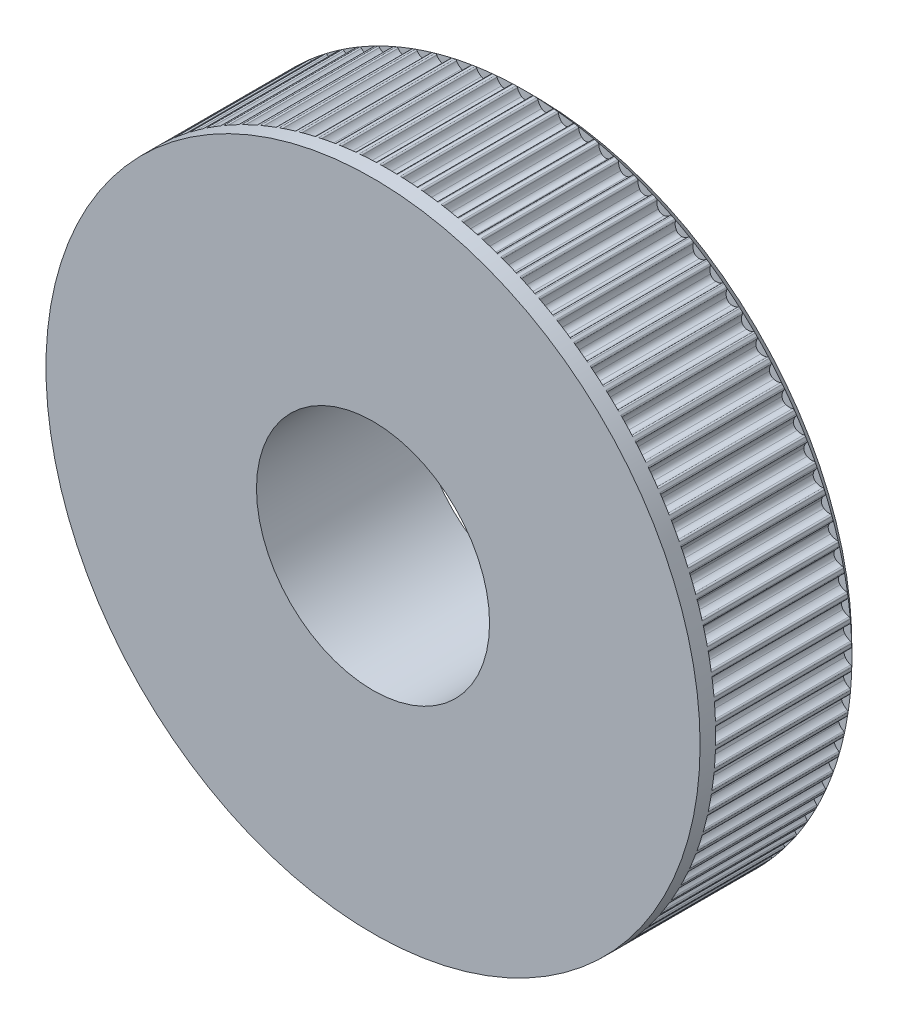
SolidWorks part; units mm, degrees
ref_plane "Front Plane" through (0, 0, 0) normal (0, 0, 1) x (1, 0, 0)
ref_plane "Top Plane" through (0, 0, 0) normal (0, 1, 0) x (1, 0, 0)
ref_plane "Right Plane" through (0, 0, 0) normal (1, 0, 0) x (0, 0, -1)
sketch "Sketch1" plane through (0, 0, 0) normal (0, 0, 1) x (1, 0, 0)
  line L3 (0, 31.5722) -> (1.999, 31.5089) construction
  line L4 (0, 0) -> (0, 30.8222) construction
  line L5 (0, 30.8222) -> (0, 32.1035) construction
  line L15 (1.999, 31.5089) -> (2.0367, 32.1035)
  line L16 (2.0367, 32.1035) -> (-2.0367, 32.1035)
  line L17 (0, 30.8222) -> (0.1538, 30.8222) construction
  line L18 (-1.999, 31.5089) -> (-2.0367, 32.1035)
  circle A0 centre (0, 0) radius 31.826 construction
  circle A1 centre (0, 0) radius 31.5722 construction
  circle A2 centre (0, 0) radius 31.3182 construction
  arc A10 (0.8511, 31.5607) -> (1.999, 31.5089) centre (0, 0) cw
  arc A11 (-0.3168, 30.9215) -> (0.3168, 30.9215) centre (0, 31.3772) ccw
  arc A12 (0.3168, 30.9215) -> (0.7035, 31.4541) centre (-0.254, 31.7426) ccw
  arc A13 (0.7035, 31.4541) -> (0.8511, 31.5607) centre (0.8471, 31.4108) cw
  arc A14 (-0.8511, 31.5607) -> (-1.999, 31.5089) centre (0, 0) ccw
  arc A15 (-0.7035, 31.4541) -> (-0.8511, 31.5607) centre (-0.8471, 31.4108) ccw
  arc A16 (-0.3168, 30.9215) -> (-0.7035, 31.4541) centre (0.254, 31.7426) cw
  point P11 (0, 31.826)
  point P13 (0, 31.5722)
  point P14 (0, 31.3182)
  dimension "D2" = 0.2775
sketch "Sketch2" plane through (0, 0, 0) normal (1, 0, 0) x (0, 0, -1)
  line L0 (-3.625, 11.25) -> (9.525, 11.25)
  line L3 (-3.625, 11.25) -> (-3.625, 31.5722)
  line L9 (9.525, 31.5722) -> (9.525, 11.25)
  line L10 (-9.525, 0) -> (9.525, 0) construction
  line L16 (-3.625, 31.5722) -> (9.525, 31.5722)
  point P25 (9.525, 0)
  point P26 (-3.625, 0)
  dimension "OA" = 19.05
  dimension "Bore" = 22.5
  dimension "Outside Width" = 13.15
revolve "Revolve1" add sketch "Sketch2" angle 360 mid plane about L10
sketch "Sketch3" plane through (0, 0, 0) normal (0, 0, 1) x (1, 0, 0)
  line L3 (1.999, 31.5089) -> (2.0367, 32.1035) construction
  line L4 (-1.999, 31.5089) -> (-2.0367, 32.1035) construction
  line L5 (2.0367, 32.1035) -> (-2.0367, 32.1035) construction
  line L6 (1.999, 31.5089) -> (2.0367, 32.1035)
  line L7 (-1.999, 31.5089) -> (-2.0367, 32.1035)
  line L8 (2.0367, 32.1035) -> (-2.0367, 32.1035)
  arc A0 (1.999, 31.5089) -> (0.8511, 31.5607) centre (0, 0) ccw construction
  arc A1 (0.8511, 31.5607) -> (0.7035, 31.4541) centre (0.8471, 31.4108) ccw construction
  arc A3 (0.3168, 30.9215) -> (0.7035, 31.4541) centre (-0.254, 31.7426) ccw construction
  arc A4 (-0.3168, 30.9215) -> (0.3168, 30.9215) centre (0, 31.3772) ccw construction
  arc A5 (-0.7035, 31.4541) -> (-0.3168, 30.9215) centre (0.254, 31.7426) ccw construction
  arc A6 (-0.7035, 31.4541) -> (-0.8511, 31.5607) centre (-0.8471, 31.4108) ccw construction
  arc A7 (-0.8511, 31.5607) -> (-1.999, 31.5089) centre (0, 0) ccw construction
  arc A8 (1.999, 31.5089) -> (0.8511, 31.5607) centre (0, 0) ccw
  arc A9 (0.8511, 31.5607) -> (0.7035, 31.4541) centre (0.8471, 31.4108) ccw
  arc A10 (0.3168, 30.9215) -> (0.7035, 31.4541) centre (-0.254, 31.7426) ccw
  arc A11 (-0.3168, 30.9215) -> (0.3168, 30.9215) centre (0, 31.3772) ccw
  arc A12 (-0.7035, 31.4541) -> (-0.3168, 30.9215) centre (0.254, 31.7426) ccw
  arc A13 (-0.7035, 31.4541) -> (-0.8511, 31.5607) centre (-0.8471, 31.4108) ccw
  arc A14 (-0.8511, 31.5607) -> (-1.999, 31.5089) centre (0, 0) ccw
extrude "Cut-Extrude1" cut sketch "Sketch3" against normal through all from surface starting at face at (11.25, 0, 3.625)
pattern_circular "CirPattern1" count 100 over 360 about axis through (0, 0, 9.525) along (0, 0, 1) of "Cut-Extrude1"
ref_axis "Center Axis 1" through (0, 0, -9.525) along (0, 0, 1)
ref_plane "Contact Plane 2" through (0, 0, -9.525) normal (0, 0, -1) x (-1, 0, 0)
sketch "Sketch7" plane through (0, 0, 3.625) normal (0, 0, 1) x (1, 0, 0)
  circle A0 centre (0, 0) radius 31.5722
  circle A1 centre (0, 0) radius 11.25
  circle A2 centre (0, 0) radius 11.25 construction
extrude "Boss-Extrude1" add sketch "Sketch7" along normal blind 1.5
sketch "Sketch8" plane through (0, 0, -9.525) normal (0, 0, -1) x (-1, 0, 0)
  circle A0 centre (0, 0) radius 31.5722
  circle A1 centre (0, 0) radius 11.25
  circle A2 centre (0, 0) radius 11.25 construction
extrude "Boss-Extrude2" add sketch "Sketch8" along normal blind 1
chamfer "Chamfer1" distance 1 angle 45 1 edges at (-31.5722, 0, -10.525)
equation "\"D2@Sketch1\" = \"R3@Sketch1\"/2"
